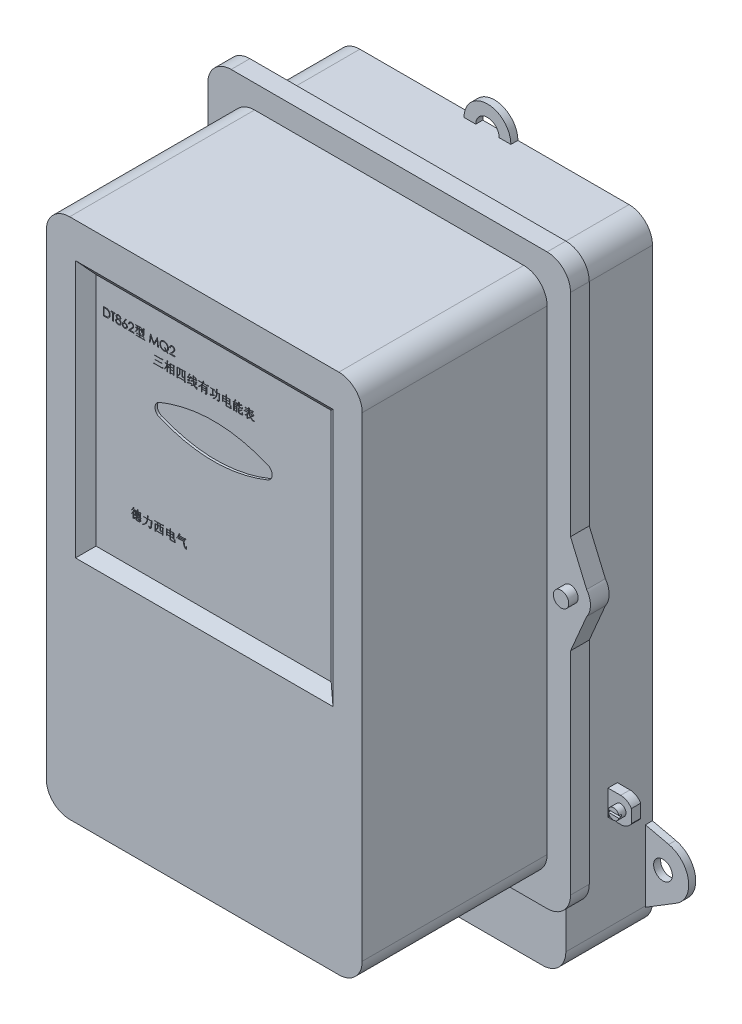
SolidWorks part; units mm, degrees
ref_plane "前视基准面" through (0, 0, 0) normal (0, 0, 1) x (1, 0, 0)
ref_plane "上视基准面" through (0, 0, 0) normal (0, 1, 0) x (1, 0, 0)
ref_plane "右视基准面" through (0, 0, 0) normal (1, 0, 0) x (0, 0, -1)
sketch "草图1" plane through (0, 0, 0) normal (0, 0, 1) x (1, 0, 0)
  line L0 (67.5, -142.0234) -> (67.5, -111.5)
  line L1 (67.5, 111.5) -> (-67.5, 111.5)
  line L2 (67.5, 111.5) -> (67.5, -111.5)
  line L3 (67.5, -111.5) -> (-67.5, -111.5)
  line L4 (-67.5, 111.5) -> (-67.5, -111.5)
  line L5 (67.5, 111.5) -> (-67.5, -111.5) construction
  line L6 (67.5, -111.5) -> (-67.5, 111.5) construction
  line L7 (67.5, -151.5) -> (-67.5, -151.5)
  line L8 (-67.5, -151.5) -> (-67.5, -142.0234)
  line L9 (0, 116.5) -> (0, -124.5) construction
  line L10 (75, -124.5) -> (-75, -124.5) construction
  line L11 (-67.5, -142.0234) -> (-67.5, -111.6183)
  line L12 (-86, 0) -> (86, 0) construction
  line L13 (-67.5, -111.5) -> (-67.5, -111.6183)
  line L14 (67.5, -142.0234) -> (67.5, -151.5)
  line L15 (77.5, 111.5) -> (77.5, 21.1121)
  line L16 (67.5, 121.5) -> (-67.5, 121.5)
  line L17 (-77.5, 111.5) -> (-77.5, 21.1121)
  line L18 (-77.4531, -113.777) -> (-67.5, -111.5)
  line L19 (-80.761, -133.8708) -> (-67.5, -142.0234)
  line L20 (80.761, -133.8708) -> (67.5, -142.0234)
  line L21 (77.4531, -113.777) -> (67.5, -111.5)
  line L22 (-84.3849, 5) -> (-77.5, 21.1121)
  line L23 (-84.3849, -5) -> (-77.5, -21.1121)
  line L24 (84.3849, -5) -> (77.5, -21.1121)
  line L25 (84.3849, 5) -> (77.5, 21.1121)
  line L26 (-77.5, -21.1121) -> (-77.5, -111.5)
  line L27 (67.5, -121.5) -> (-67.5, -121.5)
  line L28 (-77.5, 121.5) -> (-77.5, -111.5) construction
  line L29 (77.5, 121.5) -> (-77.5, 121.5) construction
  line L30 (77.5, 121.5) -> (77.5, -111.5) construction
  line L31 (67.5, -121.5) -> (-67.5, -121.5) construction
  line L32 (77.5, -21.1121) -> (77.5, -111.5)
  line L33 (72.8896, -89.886) -> (67.5, -89.886)
  line L34 (-55, 96.5) -> (55, 96.5)
  line L35 (-55, 96.5) -> (-55, -13.5)
  line L36 (-55, -13.5) -> (55, -13.5)
  line L37 (55, 96.5) -> (55, -13.5)
  line L38 (-55, 96.5) -> (55, -13.5) construction
  line L39 (-55, -13.5) -> (55, 96.5) construction
  line L40 (72.8896, -100.6652) -> (67.5, -100.6652)
  arc A0 (10, 111.5) -> (-10, 111.5) centre (0, 111.5) ccw
  arc A1 (5, 111.5) -> (-5, 111.5) centre (0, 111.5) ccw
  arc A2 (-77.4531, -113.777) -> (-80.761, -133.8708) centre (-75, -124.5) ccw
  arc A3 (80.761, -133.8708) -> (77.4531, -113.777) centre (75, -124.5) ccw
  circle A4 centre (75, -124.5) radius 4
  circle A5 centre (-75, -124.5) radius 4
  arc A6 (-84.3849, 5) -> (-84.3849, -5) centre (-77.4531, 0) ccw
  arc A7 (84.3849, 5) -> (84.3849, -5) centre (77.4531, 0) cw
  circle A8 centre (-77.4531, 0) radius 3.2917
  circle A9 centre (77.4531, 0) radius 3.2917
  arc A10 (-77.5, 111.5) -> (-67.5, 121.5) centre (-67.5, 111.5) cw
  arc A11 (77.5, 111.5) -> (67.5, 121.5) centre (67.5, 111.5) ccw
  arc A12 (77.5, -111.5) -> (67.5, -121.5) centre (67.5, -111.5) cw
  arc A13 (-67.5, -121.5) -> (-77.5, -111.5) centre (-67.5, -111.5) cw
  arc A14 (72.8896, -100.6652) -> (72.8896, -89.886) centre (72.8896, -95.2756) ccw
  circle A15 centre (72.8896, -95.2756) radius 2.3116
  point P0 (0, 0)
  point P43 (0, 41.5)
  dimension "D4" = 20
  dimension "D5" = 10
  dimension "D8" = 22
  dimension "D9" = 22
  dimension "D10" = 8
  dimension "D11" = 8
  dimension "D15" = 10
  dimension "D1" = 223
  dimension "D2" = 135
  dimension "D3" = 40
  dimension "D6" = 241
  dimension "D7" = 150
  dimension "D12" = 172
  dimension "D13" = 10
  dimension "D16" = 110
  dimension "D17" = 110
  dimension "D18" = 15
  dimension "D14" = 10
extrude "凸台-拉伸1" add sketch "草图1" along normal blind 3 contours L0 L27 L11 L8 L7 L14 | L11 A13 L18 A2 L19 A5 | A13 L11 L13 L18 | L27 L0 L3 L13 L11 | L21 A12 L0 L20 A3 A4 | A12 L21 L0 | A1 L1 A0 | L1 L4 L3 L2 L34 L37 L36 L35 | L37 L34 L35 L36 region at (0, -136.5, 0) region at (67.838, -131.7617, 0) region at (0, -116.5, 0) region at (71.3487, -116.3286, 0) region at (0, -27.8895, 0) region at (-71.3487, -116.3286, 0) region at (-67.838, -131.7617, 0) region at (-6.913, 118.413, 0) region at (0, 41.5, 0)
extrude "凸台-拉伸3" add sketch "草图1<4>" along normal blind 37 contours L0 L27 L11 L8 L7 L14 | L27 L0 L3 L13 L11 | L1 L4 L3 L2 L34 L37 L36 L35 | L37 L34 L35 L36 region at (0, -136.5, 0) region at (0, -116.5, 0) region at (0, -27.8895, 0) region at (0, 41.5, 0)
sketch "草图1<4>" plane through (0, 0, 0) normal (0, 0, 1) x (1, 0, 0) same geometry as "草图1"
extrude "凸台-拉伸4" add sketch "草图1<5>" along normal blind 124 contours L1 L4 L3 L2 L34 L37 L36 L35 | L37 L34 L35 L36 region at (0, -27.8895, 0) region at (0, 41.5, 0)
sketch "草图1<5>" plane through (0, 0, 0) normal (0, 0, 1) x (1, 0, 0) same geometry as "草图1"
extrude "凸台-拉伸5" add sketch "草图1<6>" along normal blind 8 from offset 37 contours A14 L40 L2 L21 A12 L32 | A12 L21 L0 | L27 L0 L3 L13 L11 | A13 L11 L13 L18 | A13 L18 L4 L1 A0 L16 A10 L17 L22 A6 L23 L26 A8 | A14 L32 L24 A7 L25 L15 A11 L16 A0 L1 L2 L33 A9 | L32 A14 L33 L2 L40 A15 | A15 | A1 L1 A0 | L1 A1 region at (0, -116.5, 0) region at (71.3487, -116.3286, 0) region at (72.7585, -106.4705, 0) region at (-71.3487, -116.3286, 0) region at (67.647, -95.2756, 0) region at (-72.9326, -110.1736, 0) region at (69.8062, 10.807, 0) region at (-6.913, 118.413, 0) region at (0, 113.6221, 0) region at (72.8896, -95.2756, 0)
sketch "草图1<6>" plane through (0, 0, 0) normal (0, 0, 1) x (1, 0, 0) same geometry as "草图1"
fillet "圆角1" radius 10 8 edges at (67.5, -151.5, 18.5) (-67.5, -151.5, 18.5) (-67.5, 111.5, 18.5) (-67.5, 111.5, 84.5) (-67.5, -111.5, 84.5) (67.5, 111.5, 18.5) (67.5, 111.5, 84.5) (67.5, -111.5, 84.5)
extrude "切除-拉伸1" cut sketch "草图1<7>" against normal blind 4 draft 50 from offset 124 contours L35 L36 L37 L34
sketch "草图1<7>" plane through (0, 0, 0) normal (0, 0, 1) x (1, 0, 0) same geometry as "草图1"
extrude "凸台-拉伸6" add sketch "草图1<8>" along normal blind 4 from offset 15 contours L32 A14 L33 L2 L40 A15 | A15 region at (67.647, -95.2756, 0) region at (72.8896, -95.2756, 0)
sketch "草图1<8>" plane through (0, 0, 0) normal (0, 0, 1) x (1, 0, 0) same geometry as "草图1"
extrude "凸台-拉伸7" add sketch "草图1<9>" along normal blind 7 from offset 15 contours A15 region at (72.8896, -95.2756, 0)
sketch "草图1<9>" plane through (0, 0, 0) normal (0, 0, 1) x (1, 0, 0) same geometry as "草图1"
sketch "草图2" plane through (0, 0, 22) normal (0, 0, 1) x (1, 0, 0)
  line L1 (69.5007, -94.7756) -> (76.2786, -94.7756)
  line L2 (69.5007, -94.7756) -> (69.5007, -95.7756)
  line L3 (69.5007, -95.7756) -> (76.2786, -95.7756)
  line L4 (76.2786, -94.7756) -> (76.2786, -95.7756)
  line L5 (69.5007, -94.7756) -> (76.2786, -95.7756) construction
  line L6 (69.5007, -95.7756) -> (76.2786, -94.7756) construction
  point P0 (72.8896, -95.2756)
  dimension "D1" = 1
extrude "切除-拉伸2" cut sketch "草图2" against normal blind 1
sketch "11_0_Point" plane through (0, 0, 21) normal (0, 0, 1) x (1, 0, 0)
  point P0 (72.8896, -95.2756)
sketch "草图4" plane through (0, -151.5, 0) normal (0, -1, 0) x (1, 0, 0)
  line L2 (40, 21.3239) -> (50, 21.3239)
  line L3 (40, 17.1968) -> (50, 17.1968)
  circle A0 centre (0, 20) radius 3
  arc A1 (40, 21.3239) -> (40, 17.1968) centre (40, 19.2603) ccw
  circle A2 centre (-20, 20) radius 3
  circle A3 centre (-30, 20) radius 3
  arc A4 (50, 17.1968) -> (50, 21.3239) centre (50, 19.2603) ccw
  circle A5 centre (-50, 20) radius 3
  circle A6 centre (0, 20) radius 3
  circle A8 centre (-20, 20) radius 3
  circle A9 centre (-30, 20) radius 3
  circle A11 centre (10, 20) radius 3
  circle A12 centre (0, 20) radius 3
  circle A14 centre (-20, 20) radius 3
  circle A15 centre (-30, 20) radius 3
  circle A17 centre (10, 20) radius 3
  circle A18 centre (0, 20) radius 3
  circle A20 centre (-20, 20) radius 3
  circle A21 centre (30, 20) radius 3
  circle A23 centre (10, 20) radius 3
  circle A24 centre (0, 20) radius 3
  circle A27 centre (30, 20) radius 3
  circle A29 centre (10, 20) radius 3
  circle A30 centre (0, 20) radius 3
  circle A31 centre (10, 20) radius 3
  circle A33 centre (30, 20) radius 3
  circle A36 centre (-40, 20) radius 1.9222
  circle A37 centre (-10, 20) radius 1.9222
  circle A38 centre (20, 20) radius 1.9222
  circle A39 centre (-40, 20) radius 3 [skipped]
  circle A40 centre (-40, 20) radius 3 [skipped]
  circle A41 centre (-10, 20) radius 3 [skipped]
  circle A42 centre (-10, 20) radius 3 [skipped]
  circle A43 centre (-10, 20) radius 3 [skipped]
  circle A44 centre (-10, 20) radius 3 [skipped]
  circle A45 centre (-10, 20) radius 3 [skipped]
  circle A46 centre (20, 20) radius 3 [skipped]
  circle A47 centre (20, 20) radius 3 [skipped]
  circle A48 centre (20, 20) radius 3 [skipped]
  circle A49 centre (20, 20) radius 3 [skipped]
  arc A50 (40, 23) -> (40, 17) centre (40, 20) ccw [skipped]
  arc A51 (50, 17) -> (50, 23) centre (50, 20) ccw [skipped]
  arc A52 (40, 23) -> (40, 17) centre (40, 20) ccw [skipped]
  dimension "D1" = 6
  dimension "D2" = 6
  dimension "D3" = 6
extrude "切除-拉伸3" cut sketch "草图4" against normal blind 2 contours A5 | A36 | A3 | A2 | A37 | A0 | A11 | A38 | A21 | L3 A4 L2 A1
sketch "草图5" plane through (0, -151.5, 0) normal (0, -1, 0) x (1, 0, 0)
  text T0 "\r\n     1    2       3    4      5      6      7     8     9     10  11 "
extrude "切除-拉伸4" cut sketch "草图5" against normal blind 1
sketch "草图6" plane through (0, -149.5, 0) normal (0, -1, 0) x (1, 0, 0)
  point P0 (-50, 20)
  point P1 (-40, 20)
  point P3 (-30, 20)
  point P5 (-20, 20)
  point P7 (-10, 20)
  point P9 (0, 20)
  point P11 (10, 20)
  point P13 (20, 20)
  point P15 (30, 20)
  point P17 (40, 19.2603)
  point P19 (50, 19.2603)
sketch "草图7" plane through (0, 0, 19) normal (0, 0, 1) x (1, 0, 0)
  text T0 "PE" font "Century Gothic" height 3.5
extrude "切除-拉伸5" cut sketch "草图7" against normal blind 1
sketch "草图8" plane through (0, 0, 120) normal (0, 0, 1) x (1, 0, 0)
  line L0 (0, 0) -> (0, 55.2207) construction
  line L1 (-29.1898, 55.2207) -> (29.1898, 55.2207) construction
  arc A0 (23.1535, 57.9992) -> (23.1535, 52.4422) centre (22.0221, 55.2207) cw
  arc A1 (-23.1535, 52.4422) -> (-23.1535, 57.9992) centre (-22.0221, 55.2207) cw
  spline S0 degree 3 poles (-23.1535, 57.9992) (-15.4357, 61.142) (0, 64.2847) (15.4357, 61.142) (23.1535, 57.9992) knots 0.103397 0.103397 0.103397 0.103397 0.5 0.896603 0.896603 0.896603 0.896603
  spline S1 degree 3 poles (-23.1535, 52.4422) (-15.4357, 49.2994) (0, 46.1567) (15.4357, 49.2994) (23.1535, 52.4422) knots 0.103397 0.103397 0.103397 0.103397 0.5 0.896603 0.896603 0.896603 0.896603
  text T0 "\r\n\r\n  DT862型 MQ2\r\n                  三相四线有功电能表\r\n  \r\n\r\n\r\n\r\n\r\n\r\n\r\n\r\n           德力西电气"
  dimension "D1" = 3
extrude "切除-拉伸6" cut sketch "草图8" against normal blind 1
extrude "凸台-拉伸8" add sketch "草图1<10>" along normal blind 15 from offset 34 contours A9 | A8
sketch "草图1<10>" plane through (0, 0, 0) normal (0, 0, 1) x (1, 0, 0) same geometry as "草图1"
sketch "0_0_Point" plane through (0, -149.5, 0) normal (0, -1, 0) x (1, 0, 0)
  point P0 (-50, 20)
other "0_0" parameters "直径"=2, "端头长度"=2
ref_axis "基准轴1" through (-50, -159.5, 20) along (0, 1, 0)
sketch "1_0_Point" plane through (0, -149.5, 0) normal (0, -1, 0) x (1, 0, 0)
  point P0 (-40, 20)
other "1_0" parameters "直径"=2, "端头长度"=2
ref_axis "基准轴2" through (-40, -159.5, 20) along (0, 1, 0)
sketch "2_0_Point" plane through (0, -149.5, 0) normal (0, -1, 0) x (1, 0, 0)
  point P0 (-30, 20)
other "2_0" parameters "直径"=2, "端头长度"=2
ref_axis "基准轴3" through (-30, -159.5, 20) along (0, 1, 0)
sketch "3_0_Point" plane through (0, -149.5, 0) normal (0, -1, 0) x (1, 0, 0)
  point P0 (-20, 20)
other "3_0" parameters "直径"=2, "端头长度"=2
ref_axis "基准轴4" through (-20, -159.5, 20) along (0, 1, 0)
sketch "4_0_Point" plane through (0, -149.5, 0) normal (0, -1, 0) x (1, 0, 0)
  point P0 (-10, 20)
other "4_0" parameters "直径"=2, "端头长度"=2
ref_axis "基准轴5" through (-10, -159.5, 20) along (0, 1, 0)
sketch "5_0_Point" plane through (0, -149.5, 0) normal (0, -1, 0) x (1, 0, 0)
  point P0 (0, 20)
other "5_0" parameters "直径"=2, "端头长度"=2
ref_axis "基准轴6" through (0, -159.5, 20) along (0, 1, 0)
sketch "6_0_Point" plane through (0, -149.5, 0) normal (0, -1, 0) x (1, 0, 0)
  point P0 (10, 20)
other "6_0" parameters "直径"=2, "端头长度"=2
ref_axis "基准轴7" through (10, -159.5, 20) along (0, 1, 0)
sketch "7_0_Point" plane through (0, -149.5, 0) normal (0, -1, 0) x (1, 0, 0)
  point P0 (20, 20)
other "7_0" parameters "直径"=2, "端头长度"=2
ref_axis "基准轴8" through (20, -159.5, 20) along (0, 1, 0)
sketch "8_0_Point" plane through (0, -149.5, 0) normal (0, -1, 0) x (1, 0, 0)
  point P0 (30, 20)
other "8_0" parameters "直径"=2, "端头长度"=2
ref_axis "基准轴9" through (30, -159.5, 20) along (0, 1, 0)
sketch "9_0_Point" plane through (0, -149.5, 0) normal (0, -1, 0) x (1, 0, 0)
  point P0 (40, 19.2603)
other "9_0" parameters "直径"=2, "端头长度"=2
ref_axis "基准轴10" through (40, -159.5, 19.2603) along (0, 1, 0)
sketch "10_0_Point" plane through (0, -149.5, 0) normal (0, -1, 0) x (1, 0, 0)
  point P0 (50, 19.2603)
other "10_0" parameters "直径"=2, "端头长度"=2
ref_axis "基准轴11" through (50, -159.5, 19.2603) along (0, 1, 0)
other "11_0"
ref_axis "基准轴12" through (72.8896, -95.2756, 31) along (0, 0, -1)
